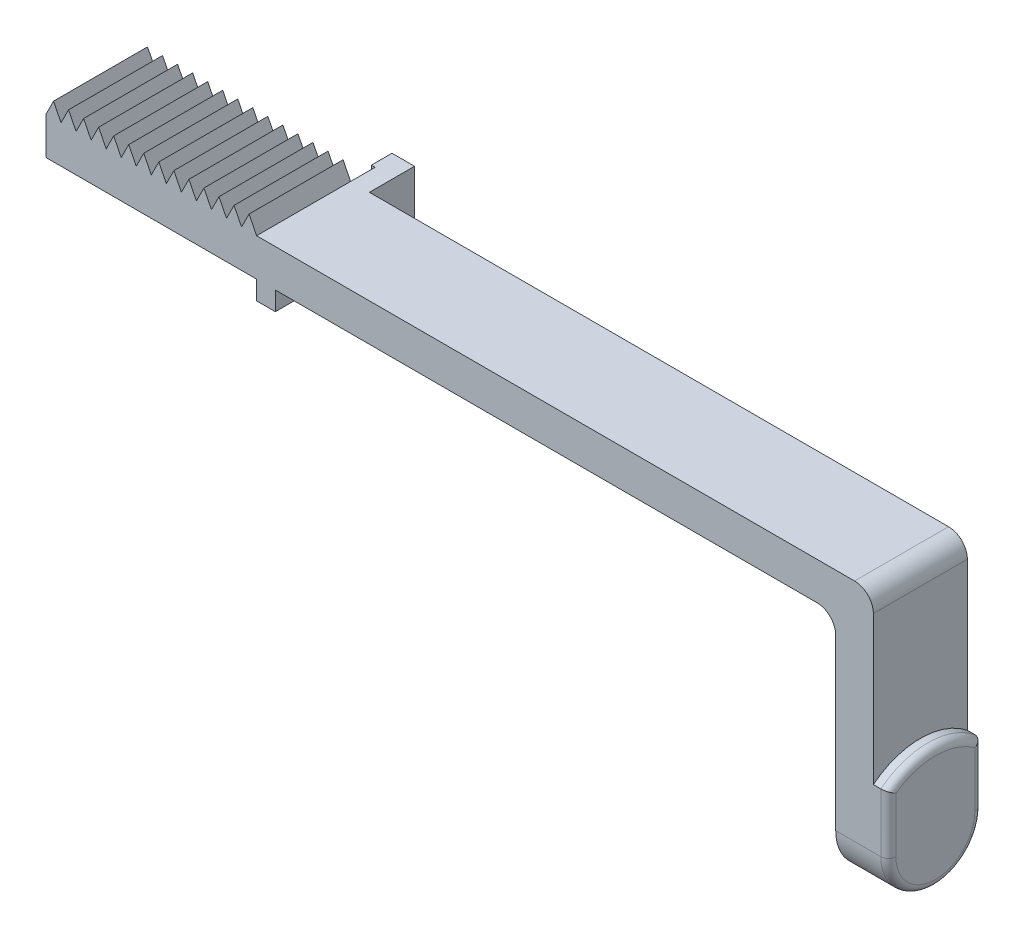
SolidWorks part; units mm, degrees
ref_plane "Plan de face" through (0, 0, 0) normal (0, 0, 1) x (1, 0, 0)
ref_plane "Plan de dessus" through (0, 0, 0) normal (0, 1, 0) x (1, 0, 0)
ref_plane "Plan de droite" through (0, 0, 0) normal (1, 0, 0) x (0, 0, -1)
sketch "Esquisse1" plane through (0, 0, 0) normal (0, 0, 1) x (1, 0, 0)
  line L1 (-214.7011, 1.8406) -> (5.2989, 1.8406)
  line L2 (-214.7011, 1.8406) -> (-214.7011, -8.1594)
  line L3 (-214.7011, -8.1594) -> (5.2989, -8.1594)
  line L4 (5.2989, 1.8406) -> (5.2989, -8.1594)
  line L5 (-214.7011, 1.8406) -> (5.2989, -8.1594) construction
  line L6 (-214.7011, -8.1594) -> (5.2989, 1.8406) construction
  line L7 (5.2989, -8.1594) -> (-4.7011, -8.1594)
  line L8 (5.2989, -8.1594) -> (5.2989, -78.1594)
  line L9 (5.2989, -78.1594) -> (-4.7011, -78.1594)
  line L10 (-4.7011, -8.1594) -> (-4.7011, -78.1594)
  point P0 (-104.7011, -3.1594)
  dimension "D1" = 220
  dimension "D2" = 10
  dimension "D3" = 10
  dimension "D4" = 70
extrude "Boss.-Extru.1" add sketch "Esquisse1" along normal blind 25 contours L4 L1 L2 L3 | L3 L10 L9 L8 region at (-104.7011, -3.1594, 0) region at (0.2989, -43.1594, 0)
ref_plane "Plan1" through (0, 0, 12.5) normal (0, 0, 1) x (1, 0, 0)
sketch "Esquisse2" plane through (0, 0, 12.5) normal (0, 0, 1) x (1, 0, 0)
  line L0 (-214.7011, 1.8406) -> (-212.7011, 5.8406)
  line L1 (-212.7011, 5.8406) -> (-210.7011, 1.8406)
  line L2 (-214.7011, 1.8406) -> (5.2989, 1.8406) construction
  line L3 (-210.7011, 1.8406) -> (-208.7011, 5.8406)
  line L4 (-208.7011, 5.8406) -> (-206.7011, 1.8406)
  line L5 (-210.7011, 1.8406) -> (-214.7011, 1.8406)
  line L6 (-206.7011, 1.8406) -> (-210.7011, 1.8406)
  line L43 (-206.7011, 1.8406) -> (-210.7011, 1.8406)
  line L48 (-210.7011, 1.8406) -> (-208.7011, 5.8406)
  line L49 (-208.7011, 5.8406) -> (-206.7011, 1.8406)
  line L50 (-206.7011, 1.8406) -> (-204.7011, 5.8406)
  line L51 (-204.7011, 5.8406) -> (-202.7011, 1.8406)
  line L52 (-202.7011, 1.8406) -> (-206.7011, 1.8406)
  line L53 (-202.7011, 1.8406) -> (-206.7011, 1.8406)
  line L54 (-206.7011, 1.8406) -> (-204.7011, 5.8406)
  line L55 (-204.7011, 5.8406) -> (-202.7011, 1.8406)
  line L56 (-202.7011, 1.8406) -> (-200.7011, 5.8406)
  line L57 (-200.7011, 5.8406) -> (-198.7011, 1.8406)
  line L58 (-198.7011, 1.8406) -> (-202.7011, 1.8406)
  line L59 (-198.7011, 1.8406) -> (-202.7011, 1.8406)
  line L60 (-202.7011, 1.8406) -> (-200.7011, 5.8406)
  line L61 (-200.7011, 5.8406) -> (-198.7011, 1.8406)
  line L62 (-198.7011, 1.8406) -> (-196.7011, 5.8406)
  line L63 (-196.7011, 5.8406) -> (-194.7011, 1.8406)
  line L64 (-194.7011, 1.8406) -> (-198.7011, 1.8406)
  line L65 (-194.7011, 1.8406) -> (-198.7011, 1.8406)
  line L66 (-198.7011, 1.8406) -> (-196.7011, 5.8406)
  line L67 (-196.7011, 5.8406) -> (-194.7011, 1.8406)
  line L68 (-194.7011, 1.8406) -> (-192.7011, 5.8406)
  line L69 (-192.7011, 5.8406) -> (-190.7011, 1.8406)
  line L70 (-190.7011, 1.8406) -> (-194.7011, 1.8406)
  line L71 (-190.7011, 1.8406) -> (-194.7011, 1.8406)
  line L72 (-194.7011, 1.8406) -> (-192.7011, 5.8406)
  line L73 (-192.7011, 5.8406) -> (-190.7011, 1.8406)
  line L74 (-190.7011, 1.8406) -> (-188.7011, 5.8406)
  line L75 (-188.7011, 5.8406) -> (-186.7011, 1.8406)
  line L76 (-186.7011, 1.8406) -> (-190.7011, 1.8406)
  line L77 (-186.7011, 1.8406) -> (-190.7011, 1.8406)
  line L78 (-190.7011, 1.8406) -> (-188.7011, 5.8406)
  line L79 (-188.7011, 5.8406) -> (-186.7011, 1.8406)
  line L80 (-186.7011, 1.8406) -> (-184.7011, 5.8406)
  line L81 (-184.7011, 5.8406) -> (-182.7011, 1.8406)
  line L82 (-182.7011, 1.8406) -> (-186.7011, 1.8406)
  line L83 (-182.7011, 1.8406) -> (-186.7011, 1.8406)
  line L84 (-186.7011, 1.8406) -> (-184.7011, 5.8406)
  line L85 (-184.7011, 5.8406) -> (-182.7011, 1.8406)
  line L86 (-182.7011, 1.8406) -> (-180.7011, 5.8406)
  line L87 (-180.7011, 5.8406) -> (-178.7011, 1.8406)
  line L88 (-178.7011, 1.8406) -> (-182.7011, 1.8406)
  line L89 (-178.7011, 1.8406) -> (-182.7011, 1.8406)
  line L90 (-182.7011, 1.8406) -> (-180.7011, 5.8406)
  line L91 (-180.7011, 5.8406) -> (-178.7011, 1.8406)
  line L92 (-178.7011, 1.8406) -> (-176.7011, 5.8406)
  line L93 (-176.7011, 5.8406) -> (-174.7011, 1.8406)
  line L94 (-174.7011, 1.8406) -> (-178.7011, 1.8406)
  line L95 (-174.7011, 1.8406) -> (-178.7011, 1.8406)
  line L96 (-178.7011, 1.8406) -> (-176.7011, 5.8406)
  line L97 (-176.7011, 5.8406) -> (-174.7011, 1.8406)
  line L98 (-174.7011, 1.8406) -> (-172.7011, 5.8406)
  line L99 (-172.7011, 5.8406) -> (-170.7011, 1.8406)
  line L100 (-170.7011, 1.8406) -> (-174.7011, 1.8406)
  line L101 (-170.7011, 1.8406) -> (-174.7011, 1.8406)
  line L102 (-174.7011, 1.8406) -> (-172.7011, 5.8406)
  line L103 (-172.7011, 5.8406) -> (-170.7011, 1.8406)
  line L104 (-170.7011, 1.8406) -> (-168.7011, 5.8406)
  line L105 (-168.7011, 5.8406) -> (-166.7011, 1.8406)
  line L106 (-166.7011, 1.8406) -> (-170.7011, 1.8406)
  line L107 (-166.7011, 1.8406) -> (-170.7011, 1.8406)
  line L108 (-170.7011, 1.8406) -> (-168.7011, 5.8406)
  line L109 (-168.7011, 5.8406) -> (-166.7011, 1.8406)
  line L110 (-166.7011, 1.8406) -> (-164.7011, 5.8406)
  line L111 (-164.7011, 5.8406) -> (-162.7011, 1.8406)
  line L112 (-162.7011, 1.8406) -> (-166.7011, 1.8406)
  line L113 (-162.7011, 1.8406) -> (-166.7011, 1.8406)
  line L114 (-166.7011, 1.8406) -> (-164.7011, 5.8406)
  line L115 (-164.7011, 5.8406) -> (-162.7011, 1.8406)
  line L116 (-162.7011, 1.8406) -> (-160.7011, 5.8406)
  line L117 (-160.7011, 5.8406) -> (-158.7011, 1.8406)
  line L118 (-158.7011, 1.8406) -> (-162.7011, 1.8406)
  dimension "D1" = 4
  dimension "D2" = 4
  dimension "D3" = 2
  dimension "D4" = 4
  dimension "D5" = 2
  dimension "D6" = 4
  dimension "D7" = 13
extrude "Boss.-Extru.2" add sketch "Esquisse2" along normal mid plane 25 contours L78 | L71 L73 L72 | L69 | L65 L67 L66 | L63 | L57 | L51 | L43 L49 L48 | L5 L1 L0 | L6 L4 L3 | L74 L75 L76 | L60 L61 L59 | L54 L55 L53 | L80 L81 L82 | L83 L84 L85 | L86 L87 L88 | L89 L90 L91 | L92 L93 L94 | L95 L96 L97 | L98 L99 L100 | L101 L102 L103 | L104 L105 L106 | L107 L108 L109 | L110 L111 L112 | L113 L114 L115 | L116 L117 L118 region at (-188.7011, 3.1739, 12.5) region at (-192.7011, 3.1739, 12.5) region at (-196.7011, 3.1739, 12.5) region at (-200.7011, 3.1739, 12.5) region at (-204.7011, 3.1739, 12.5) region at (-208.7011, 3.1739, 12.5) region at (-212.7011, 3.1739, 12.5)
sketch "Esquisse3" plane through (-4.7011, 0, 0) normal (-1, 0, 0) x (0, 0, 1)
  line L0 (12.5, -45.1) -> (12.5, 45.1) construction
  line L1 (25, -78.1594) -> (0, -78.1594) construction
  circle A0 centre (12.5, -58.1594) radius 20
  circle A1 centre (12.5, -58.1594) radius 15
  dimension "D1" = 40
  dimension "D2" = 20
  dimension "D3" = 30
extrude "Boss.-Extru.3" add sketch "Esquisse3" against normal blind 10
sketch "Esquisse4" plane through (-4.7011, 0, 0) normal (-1, 0, 0) x (0, 0, 1)
  circle A0 centre (12.5, -58.1594) radius 20
  circle A1 centre (12.5, -58.1594) radius 15
  circle A2 centre (12.5, -58.1594) radius 24.6712
  line M5 (0, -73.7719) -> (0, -78.1594)
  line M6 (0, -78.1594) -> (25, -78.1594)
  line M7 (25, -78.1594) -> (25, -73.7719)
  line M11 (0, -49.8678) -> (0, -66.451)
  line M14 (25, -66.451) -> (25, -49.8678)
extrude "Enlèv. mat.-Extru.1" cut sketch "Esquisse4" against normal through all contours A1 M14 M11 | A0 M6 M7 | A0 M5 M6 region at (-4.7011, -76.8722, 3.0523) region at (-4.7011, -76.8722, 21.9477) region at (-4.7011, -58.1594, 12.5)
sketch "Esquisse5" plane through (-214.7011, 0, 0) normal (-1, 0, 0) x (0, 0, 1)
  line L0 (25, -8.1594) -> (0, -8.1594) construction
  line L1 (7.5, -8.1594) -> (17.5, -8.1594)
  line L2 (7.5, -8.1594) -> (7.5, -3.1594)
  line L3 (7.5, -3.1594) -> (17.5, -3.1594)
  line L4 (17.5, -8.1594) -> (17.5, -3.1594)
  line L5 (0, 1.8406) -> (0, -8.1594) construction
  dimension "D1" = 7.5
  dimension "D2" = 10
  dimension "D3" = 5
extrude "Enlèv. mat.-Extru.2" cut sketch "Esquisse5" against normal blind 60
sketch "Esquisse6" plane through (5.2989, 0, 0) normal (1, 0, 0) x (0, 0, -1)
  circle A0 centre (-12.5, -58.1594) radius 20
extrude "Boss.-Extru.4" add sketch "Esquisse6" along normal blind 4
sketch "Esquisse8" plane through (-214.7011, 0, 0) normal (-1, 0, 0) x (0, 0, 1)
  line L0 (12.5, 1.8406) -> (12.5, -3.1594) construction
  line L1 (25, 1.8406) -> (0, 1.8406) construction
  line L2 (17.5, -3.1594) -> (7.5, -3.1594) construction
  circle A0 centre (12.5, -0.6594) radius 2
  dimension "D1" = 4
extrude "Enlèv. mat.-Extru.4" cut sketch "Esquisse8" against normal blind 6
sketch "Esquisse9" plane through (5.2989, 0, 0) normal (-1, 0, 0) x (0, 0, 1)
  point P0 (12.5, -58.1594)
sketch "Esquisse10" plane through (0, 0, 25) normal (0, 0, 1) x (1, 0, 0)
  line L0 (-214.7011, -8.1594) -> (-4.7011, -8.1594) construction
  line L3 (-158.7011, -8.1594) -> (-153.7011, -8.1594)
  line L4 (-153.7011, 1.8406) -> (-153.7011, -8.1594)
  line L5 (-158.7011, -8.1594) -> (-158.7011, 1.8406)
  line L6 (-158.7011, 1.8406) -> (-153.7011, 1.8406)
  dimension "D1" = 5
extrude "Boss.-Extru.5" add sketch "Esquisse10" along normal blind 10
sketch "Esquisse11" plane through (0, 0, 0) normal (0, 0, -1) x (-1, 0, 0)
  line L0 (153.7011, -8.1594) -> (153.7011, -13.1594)
  line L1 (158.7011, 1.8406) -> (153.7011, 1.8406)
  line L2 (158.7011, 1.8406) -> (158.7011, -8.1594)
  line L4 (153.7011, 1.8406) -> (153.7011, -8.1594)
  line L5 (153.7011, -13.1594) -> (158.7011, -13.1594)
  line L6 (158.7011, -13.1594) -> (158.7011, -8.1594)
  dimension "D1" = 5
  dimension "D2" = 5
extrude "Boss.-Extru.6" add sketch "Esquisse11" along normal blind 12
sketch "Esquisse12" plane through (5.2989, 0, 0) normal (-1, 0, 0) x (0, 0, 1)
  circle A0 centre (12.5, -58.1594) radius 15
  circle A1 centre (12.5, -58.1594) radius 11
  dimension "D1" = 22
extrude "Boss.-Extru.8" add sketch "Esquisse12" along normal blind 10
sketch "Esquisse13" plane through (-4.7011, 0, 0) normal (-1, 0, 0) x (0, 0, 1)
  line L0 (0, -42.5469) -> (0, -58.1594)
  line L1 (0, -58.1594) -> (25, -58.1594)
  line L2 (25, -58.1594) -> (25, -42.5469)
  circle A1 centre (12.5, -58.1594) radius 12.5
  circle A2 centre (12.5, -58.1594) radius 20
  arc M2 (0, -42.5469) -> (25, -42.5469) centre (12.5, -58.1594) ccw
extrude "Enlèv. mat.-Extru.5" cut sketch "Esquisse13" against normal blind 20 contours A1 L0 L2 M2 region at (-4.7011, -50.3531, -0.5356)
fillet "Congé1" radius 2 4 edges at (9.2989, -50.3531, 0) (9.2989, -70.6594, 12.5) (9.2989, -50.3531, 25) (9.2989, -38.1594, 12.5)
sketch "Esquisse14" plane through (5.2989, 0, 0) normal (-1, 0, 0) x (0, 0, 1)
  circle A0 centre (12.5, -58.1594) radius 11
  dimension "D1" = 22
extrude "Boss.-Extru.9" add sketch "Esquisse14" along normal blind 3
fillet "Congé2" radius 5 2 edges at (-4.7011, -8.1594, 12.5) (5.2989, 1.8406, 12.5)
sketch "Esquisse16" plane through (-158.7011, 0, 0) normal (-1, 0, 0) x (0, 0, 1)
  line L0 (-12, 1.8406) -> (-12, -13.1594)
  line L1 (-12, 1.8406) -> (-6.5, 1.8406)
  line L2 (-12, -13.1594) -> (-6.5, -13.1594)
  line L3 (-6.5, 1.8406) -> (-6.5, -13.1594)
  dimension "D1" = 5.5
extrude "Boss.-Extru.10" add sketch "Esquisse16" along normal blind 1
sketch "Esquisse18" plane through (-158.7011, 0, 0) normal (-1, 0, 0) x (0, 0, 1)
  line L0 (25, 1.8406) -> (25, -8.1594)
  line L1 (25, 1.8406) -> (35.4488, 1.8406)
  line L2 (25, -8.1594) -> (35.4488, -8.1594)
  line L3 (35.4488, 1.8406) -> (35.4488, -8.1594)
extrude "Enlèv. mat.-Extru.8" cut sketch "Esquisse18" against normal blind 6
sketch "Esquisse19" plane through (0, 0, 0) normal (0, 0, 1) x (1, 0, 0)
  line L0 (-158.7011, -13.1594) -> (-153.7011, -13.1594)
  line L1 (-158.7011, -13.1594) -> (-158.7011, 1.7517)
  line L2 (-153.7011, -13.1594) -> (-153.7011, 1.7517)
  line L3 (-158.7011, 1.7517) -> (-153.7011, 1.7517)
extrude "Boss.-Extru.11" add sketch "Esquisse19" along normal blind 25
